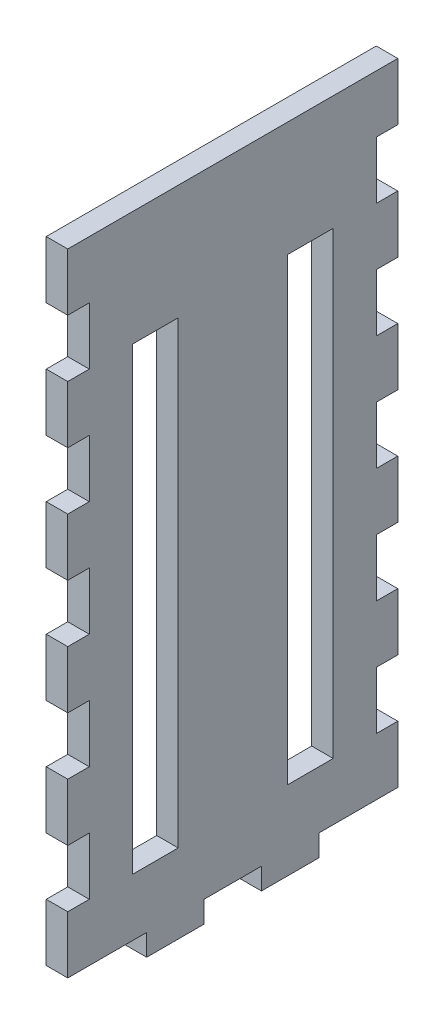
SolidWorks part; units mm, degrees
ref_plane "Front Plane" through (0, 0, 0) normal (0, 0, 1) x (1, 0, 0)
ref_plane "Top Plane" through (0, 0, 0) normal (0, 1, 0) x (1, 0, 0)
ref_plane "Right Plane" through (0, 0, 0) normal (1, 0, 0) x (0, 0, -1)
sketch "Sketch1" plane through (0, 0, 0) normal (1, 0, 0) x (0, 0, -1)
  line L1 (-63.5, -139.7) -> (63.5, -139.7)
  line L2 (-63.5, -139.7) -> (-63.5, 139.7)
  line L3 (-63.5, 139.7) -> (63.5, 139.7)
  line L4 (63.5, -139.7) -> (63.5, 139.7)
  line L5 (-63.5, -139.7) -> (63.5, 139.7) construction
  line L6 (-63.5, 139.7) -> (63.5, -139.7) construction
  point P0 (0, 0)
  dimension "D1" = 127
  dimension "D2" = 279.4
extrude "Boss-Extrude1" add sketch "Sketch1" along normal blind 9.525
sketch "Sketch2" plane through (0, 0, 63.5) normal (0, 0, 1) x (1, 0, 0)
  line L0 (0, 139.7) -> (0, -139.7) construction
  line L1 (0, 139.7) -> (9.525, 139.7)
  line L2 (0, 139.7) -> (0, 114.3)
  line L3 (0, 114.3) -> (9.525, 114.3)
  line L4 (9.525, 139.7) -> (9.525, 114.3)
  line L5 (0, -69.85) -> (0, 69.85) construction
  line L6 (9.525, 139.7) -> (9.525, -139.7) construction
  line L7 (9.525, 139.7) -> (0, 139.7) construction
  dimension "D1" = 25.4
  dimension "D2" = 0
extrude "Boss-Extrude2" add sketch "Sketch2" along normal blind 9.525
pattern_linear "LPattern1" count 6 spacing 50.8 along (0, -1, 0) of "Boss-Extrude2"
mirror "Mirror1" about plane through (0, 0, 0) normal (0, 0, 1) of "LPattern1"
sketch "Sketch3" plane through (0, -139.7, 0) normal (0, -1, 0) x (1, 0, 0)
  line L0 (0, 73.025) -> (0, -73.025) construction
  line L1 (0, 38.1) -> (9.525, 38.1)
  line L2 (0, 38.1) -> (0, 12.7)
  line L3 (0, 12.7) -> (9.525, 12.7)
  line L4 (9.525, 38.1) -> (9.525, 12.7)
  line L5 (9.525, 73.025) -> (9.525, -73.025) construction
  line L6 (0, 73.025) -> (9.525, 73.025) construction
  dimension "D1" = 34.925
  dimension "D2" = 25.4
extrude "Boss-Extrude3" add sketch "Sketch3" along normal blind 9.525
pattern_linear "LPattern2" count 2 spacing 50.8 along (0, 0, -1) of "Boss-Extrude3"
sketch "Sketch4" plane through (9.525, 0, 0) normal (1, 0, 0) x (0, 0, -1)
  line L1 (-44.45, -114.3) -> (-24.13, -114.3)
  line L3 (-44.45, 88.9) -> (-24.13, 88.9)
  line L5 (-73.025, -139.7) -> (-38.1, -139.7) construction
  line L6 (-73.025, 88.9) -> (-63.5, 88.9) construction
  line L7 (-24.13, -114.3) -> (-24.13, 88.9)
  line L8 (-44.45, -114.3) -> (-44.45, 88.9)
  line L9 (0, -139.7) -> (0, 139.7) construction
  line L10 (-12.7, -139.7) -> (12.7, -139.7) construction
  line L11 (73.025, 139.7) -> (-73.025, 139.7) construction
  point P10 (-68.2625, 88.9)
  dimension "D1" = 24.13
  dimension "D2" = 20.32
  dimension "D3" = 25.4
  dimension "D4" = 0
extrude "Cut-Extrude1" cut sketch "Sketch4" against normal blind 9.525
mirror "Mirror2" about plane through (0, 0, 0) normal (0, 0, 1) of "Cut-Extrude1"
sketch "Sketch5" plane through (0, 0, 0) normal (-1, 0, 0) x (0, 0, 1)
  circle A0 centre (-4.315, 53.4964) radius 2.5 construction
  circle A1 centre (-4.315, 53.4964) radius 2.5
  circle A2 centre (-4.315, 34.9964) radius 2.5 construction
  circle A3 centre (-4.315, 34.9964) radius 2.5
  circle A4 centre (4.315, 19.4604) radius 2.5 construction
  circle A5 centre (4.315, 19.4604) radius 2.5
  circle A6 centre (4.315, 0.9604) radius 2.5 construction
  circle A7 centre (4.315, 0.9604) radius 2.5
  circle A8 centre (-4.315, -16.5756) radius 2.5 construction
  circle A9 centre (-4.315, -16.5756) radius 2.5
  circle A10 centre (-4.315, -35.0756) radius 2.5 construction
  circle A11 centre (-4.315, -35.0756) radius 2.5
  circle A12 centre (4.315, -50.3156) radius 2.5 construction
  circle A13 centre (4.315, -50.3156) radius 2.5
  circle A14 centre (4.315, -68.8156) radius 2.5 construction
  circle A15 centre (4.315, -68.8156) radius 2.5
